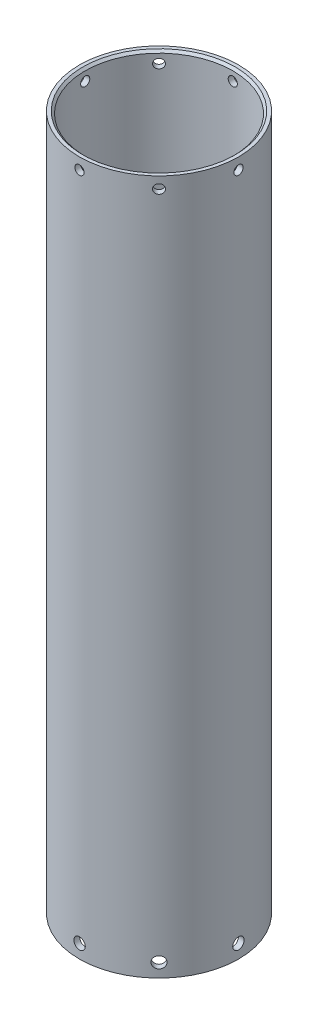
SolidWorks part; units mm, degrees
material "1060 Alloy"
ref_plane "Front Plane" through (0, 0, 0) normal (0, 0, 1) x (1, 0, 0)
ref_plane "Top Plane" through (0, 0, 0) normal (0, 1, 0) x (1, 0, 0)
ref_plane "Right Plane" through (0, 0, 0) normal (1, 0, 0) x (0, 0, -1)
sketch "Sketch2" plane through (0, 0, 0) normal (0, 0, 1) x (1, 0, 0)
  line L0 (0, 0) -> (0, 365.76) construction
  line L3 (41.275, 0) -> (44.45, 0)
  line L5 (41.275, 387.858) -> (44.45, 387.858)
  line L6 (44.45, 0) -> (44.45, 387.858)
  line L11 (41.275, 387.858) -> (41.275, 193.929)
  line L12 (41.275, 193.929) -> (41.2565, 193.9033)
  line L13 (41.275, 193.929) -> (41.275, 0)
  line L14 (0, -55) -> (0, 55) construction
  dimension "D3" = 3.175
  dimension "D4" = 387.858
revolve "Revolve1" add sketch "Sketch2" angle 360 about L0 region at (42.8625, 193.929, 0)
ref_axis "Axis1" through (0, -17.0472, 0) along (0, 1, 0)
ref_plane "Plane1" through (0, 7.62, 0) normal (0, -1, 0) x (-1, 0, 0)
ref_axis "Axis2" through (0, 7.62, 88.99) along (0, 0, -1)
hole_wizard "1/4 (0.25) Diameter Hole1" positions "3DSketch1" profile "Sketch3" hole size "1/4" standard "ANSI Inch" end condition up to next
sketch3d "3DSketch1"
  line L0 (0, 7.62, 88.99) -> (0, 7.62, -88.99) construction
  point P0 (0, 7.62, -44.45)
sketch "Sketch3" plane through (0, 7.62, -44.45) normal (1, 0, 0) x (0, 1, 0)
  line L0 (0, 0) -> (0, 3.175)
  line L1 (0, 3.175) -> (3.175, 3.175)
  line L2 (3.175, 3.175) -> (3.175, 0)
  line L5 (3.175, 0) -> (0, 0)
  line L11 (0, -6.35) -> (0, 107.95) construction
  dimension "Thru Hole Dia." = 6.35
  dimension "Thru Hole Depth" = 3.175
pattern_circular "CirPattern1" count 8 over 360 about axis through (0, -17.0472, 0) along (0, 1, 0) of "1/4 (0.25) Diameter Hole1"
ref_plane "Plane2" through (0, 381.508, 0) normal (0, 1, 0) x (1, 0, 0)
ref_axis "Axis3" through (0, 381.508, -88.99) along (0, 0, 1)
sketch "Sketch4" plane through (0, 0, 0) normal (0, 0, 1) x (1, 0, 0)
  line L0 (0, -17.0472) -> (0, 357.9914) construction
  line L1 (0, 381.508) -> (-43.7642, 381.508)
  line L2 (0, 381.508) -> (0, 378.46)
  line L3 (0, 378.46) -> (-43.7642, 378.46)
  line L4 (-43.7642, 381.508) -> (-43.7642, 378.46)
  line L5 (48.895, 381.508) -> (-48.895, 381.508) construction
  dimension "D1" = 43.7642
  dimension "D2" = 3.048
revolve "Cut-Revolve2" [suppressed] cut sketch "Sketch4" angle 360 about axis through (0, -17.0472, 0) along (0, 1, 0)
hole_wizard "Tap Drill for 1/4-20 Tap1" positions "3DSketch3" profile "Sketch6" hole size "1/4-20" standard "ANSI Inch"
sketch3d "3DSketch3"
  line L0 (0, 381.508, -88.99) -> (0, 381.508, 88.99) construction
  point P0 (0, 381.508, -44.45)
  point P3 (0, 0, 0)
sketch "Sketch6" plane through (0, 381.508, -44.45) normal (1, 0, 0) x (0, 1, 0)
  line L0 (0, 0) -> (0, 4.8358)
  line L1 (0, 4.8358) -> (2.5527, 3.302)
  line L2 (2.5527, 3.302) -> (2.5527, 0)
  line L5 (2.5527, 0) -> (0, 0)
  line L10 (0, 4.8358) -> (-2.5527, 3.302) construction
  line L11 (0, -6.35) -> (0, 107.95) construction
  dimension "Hole Dia." = 5.1054
  dimension "Hole Depth" = 3.302
  dimension "Drill Angle" = 118
pattern_circular "CirPattern2" count 8 over 360 about axis through (0, -17.0472, 0) along (0, 1, 0) of "Tap Drill for 1/4-20 Tap1" reverse direction yes
chamfer "Chamfer1" distance 1.27 angle 45 2 edges at (0, 0, -41.275) (0, 387.858, -41.275)
